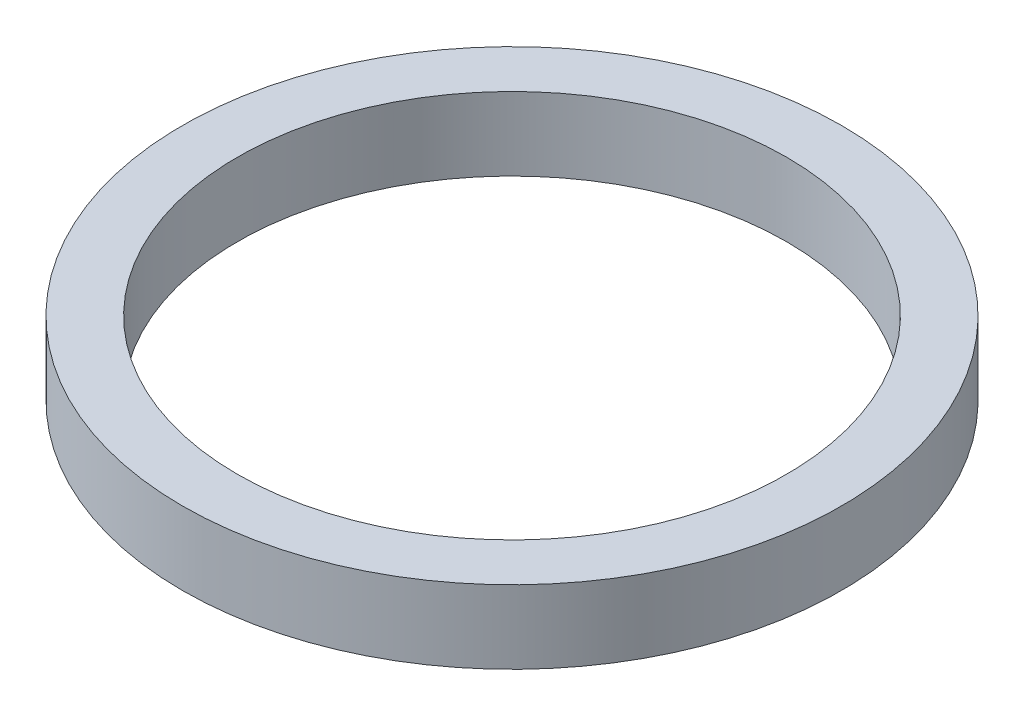
SolidWorks part; units mm, degrees
ref_plane "Front Plane" through (0, 0, 0) normal (0, 0, 1) x (1, 0, 0)
ref_plane "Top Plane" through (0, 0, 0) normal (0, 1, 0) x (1, 0, 0)
ref_plane "Right Plane" through (0, 0, 0) normal (1, 0, 0) x (0, 0, -1)
sketch "Sketch1" plane through (0, 0, 0) normal (0, 1, 0) x (1, 0, 0)
  circle A0 centre (0, 0) radius 45
  dimension "FLANGE_OD" = 90
extrude "Boss-Extrude1" add sketch "Sketch1" along normal blind 10
sketch "Sketch2" plane through (0, 0, 0) normal (0, 1, 0) x (1, 0, 0)
  circle A0 centre (0, 0) radius 37.5
  dimension "BORE_D" = 75
extrude "Cut-Extrude1" cut sketch "Sketch2" along normal through all
sketch "Sketch3" plane through (0, 10, 0) normal (0, 1, 0) x (1, 0, 0)
  circle A0 centre (0, 0) radius 20.1651 construction
  circle A1 centre (-20.1651, 0) radius 1.5
  dimension "BOLT_D" = 3
  dimension "BOLT_PCD" = 40.3302
extrude "Cut-Extrude2" cut sketch "Sketch3" against normal blind 9.004 rebuild error yes
pattern_circular "CirPattern1" count 5 over 360 rebuild error yes
